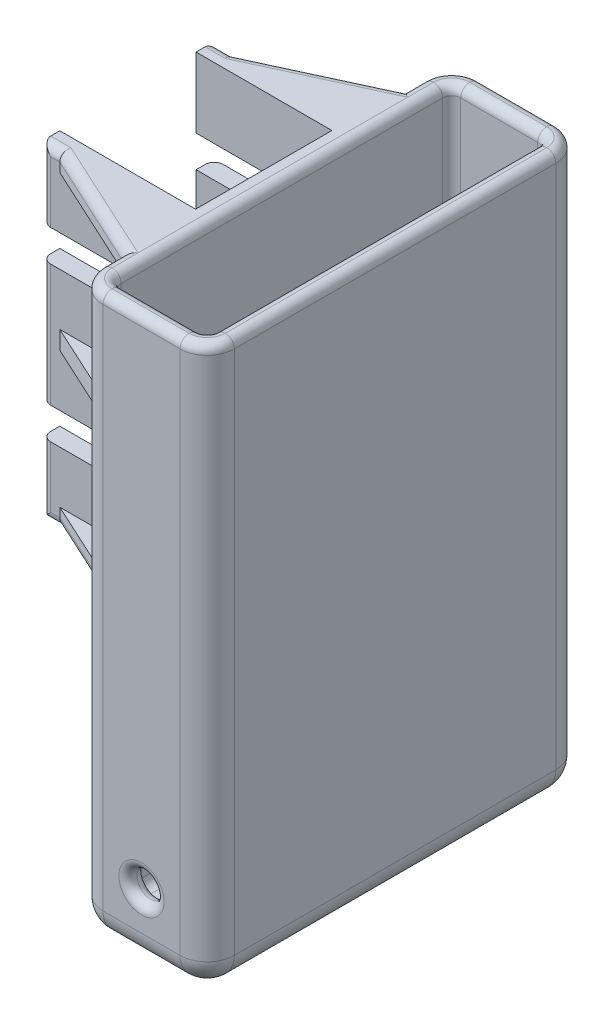
SolidWorks part; units mm, degrees
ref_plane "정면" through (0, 0, 0) normal (0, 0, 1) x (1, 0, 0)
ref_plane "윗면" through (0, 0, 0) normal (0, 1, 0) x (1, 0, 0)
ref_plane "우측면" through (0, 0, 0) normal (1, 0, 0) x (0, 0, -1)
sketch "스케치1" plane through (0, 0, 0) normal (0, 1, 0) x (1, 0, 0)
  line L1 (6, 37.5) -> (23, 37.5)
  line L2 (4, 35.5) -> (4, -35.5)
  line L3 (6, -37.5) -> (23, -37.5)
  line L4 (25, 35.5) -> (25, -35.5)
  line L5 (4, 37.5) -> (25, -37.5) construction
  line L6 (4, -37.5) -> (25, 37.5) construction
  line L7 (6, 41.5) -> (23, 41.5)
  line L8 (0, 35.5) -> (0, -35.5)
  line L9 (6, -41.5) -> (23, -41.5)
  line L10 (29, 35.5) -> (29, -35.5)
  line L11 (0, 41.5) -> (29, -41.5) construction
  line L12 (0, -41.5) -> (29, 41.5) construction
  arc A0 (23, -37.5) -> (25, -35.5) centre (23, -35.5) ccw
  arc A1 (4, -35.5) -> (6, -37.5) centre (6, -35.5) ccw
  arc A2 (23, 37.5) -> (25, 35.5) centre (23, 35.5) cw
  arc A3 (6, 37.5) -> (4, 35.5) centre (6, 35.5) ccw
  arc A4 (23, -41.5) -> (29, -35.5) centre (23, -35.5) ccw
  arc A5 (23, 41.5) -> (29, 35.5) centre (23, 35.5) cw
  arc A6 (0, -35.5) -> (6, -41.5) centre (6, -35.5) ccw
  arc A7 (6, 41.5) -> (0, 35.5) centre (6, 35.5) ccw
  point P0 (14.5, 0)
  point P5 (14.5, 0)
  point P10 (0, 0)
  dimension "D5" = 2
  dimension "D6" = 6
  dimension "D1" = 21
  dimension "D2" = 75
  dimension "D3" = 4
  dimension "D4" = 4
extrude "보스-돌출1" add sketch "스케치1" against normal blind 120
sketch "스케치2" plane through (0, -120, 0) normal (0, -1, 0) x (1, 0, 0)
  line L4 (23, 41.5) -> (6, 41.5)
  line L5 (0, 35.5) -> (0, -35.5)
  line L6 (6, -41.5) -> (23, -41.5)
  line L7 (29, -35.5) -> (29, 35.5)
  line L8 (23, 41.5) -> (6, 41.5)
  line L9 (0, 35.5) -> (0, -35.5)
  line L10 (6, -41.5) -> (23, -41.5)
  line L11 (29, -35.5) -> (29, 35.5)
  arc A4 (29, 35.5) -> (23, 41.5) centre (23, 35.5) ccw
  arc A5 (6, 41.5) -> (0, 35.5) centre (6, 35.5) ccw
  arc A6 (0, -35.5) -> (6, -41.5) centre (6, -35.5) ccw
  arc A7 (23, -41.5) -> (29, -35.5) centre (23, -35.5) ccw
  arc A8 (29, 35.5) -> (23, 41.5) centre (23, 35.5) ccw
  arc A9 (6, 41.5) -> (0, 35.5) centre (6, 35.5) ccw
  arc A10 (0, -35.5) -> (6, -41.5) centre (6, -35.5) ccw
  arc A11 (23, -41.5) -> (29, -35.5) centre (23, -35.5) ccw
  dimension "D1" = 0
extrude "보스-돌출2" add sketch "스케치2" along normal blind 4
fillet "필렛1" radius 2 8 edges at (4, -120, 0) (4.5858, -120, -36.9142) (14.5, -120, -37.5) (24.4142, -120, -36.9142) (25, -120, 0) (24.4142, -120, 36.9142) (14.5, -120, 37.5) (4.5858, -120, 36.9142)
fillet "필렛2" radius 6 8 edges at (29, -124, 0) (27.2426, -124, -39.7426) (14.5, -124, -41.5) (1.7574, -124, -39.7426) (0, -124, 0) (1.7574, -124, 39.7426) (14.5, -124, 41.5) (27.2426, -124, 39.7426)
sketch "스케치3" plane through (0, 0, 0) normal (0, 1, 0) x (1, 0, 0)
  line L0 (0, 15.05) -> (0, 19.05)
  line L1 (0, 35.5) -> (0, -35.5) construction
  line L2 (0, 19.05) -> (-30, 19.05)
  line L3 (-30, 19.05) -> (-30, 15.05)
  line L4 (-30, 15.05) -> (0, 15.05)
  line L5 (0, -15.05) -> (-30, -15.05)
  line L6 (-30, -15.05) -> (-30, -19.05)
  line L7 (-30, -19.05) -> (0, -19.05)
  line L8 (0, -19.05) -> (0, -15.05)
  line L9 (0, 15.05) -> (0, -15.05) construction
  point P10 (0, 0)
  dimension "D1" = 30.1
  dimension "D2" = 30
  dimension "D3" = 4
extrude "보스-돌출3" add sketch "스케치3" against normal blind 72
ref_plane "평면1" through (0, -36, 0) normal (0, 1, 0) x (1, 0, 0)
sketch "스케치4" plane through (0, -36, 0) normal (0, 1, 0) x (1, 0, 0)
  line L0 (0, 31.05) -> (0, 19.05)
  line L1 (0, 35.5) -> (0, 19.05) construction
  line L2 (0, 19.05) -> (-26, 19.05)
  line L3 (0, 19.05) -> (-30, 19.05) construction
  line L4 (-26, 19.05) -> (0, 31.05)
  line L5 (0, -19.05) -> (-26, -19.05)
  line L6 (-30, -19.05) -> (0, -19.05) construction
  line L7 (0, -19.05) -> (0, -35.5) construction
  line L8 (-26, -19.05) -> (0, -31.05)
  line L9 (0, -31.05) -> (0, -19.05)
  dimension "D1" = 26
  dimension "D2" = 12
  dimension "D3" = 12
  dimension "D4" = 26
extrude "보스-돌출4" add sketch "스케치4" along normal mid plane 4
sketch "스케치5" plane through (0, 0, 0) normal (0, 1, 0) x (1, 0, 0)
  line L0 (0, -31.05) -> (0, -19.05) construction
  line L1 (0, -19.05) -> (-26, -19.05) construction
  line L2 (-26, -19.05) -> (0, -31.05) construction
  line L3 (0, 31.05) -> (-26, 19.05) construction
  line L4 (-26, 19.05) -> (0, 19.05) construction
  line L5 (0, 19.05) -> (0, 31.05) construction
  line L6 (0, -31.05) -> (0, -19.05)
  line L7 (0, -19.05) -> (-26, -19.05)
  line L8 (-26, -19.05) -> (0, -31.05)
  line L9 (0, 31.05) -> (-26, 19.05)
  line L10 (-26, 19.05) -> (0, 19.05)
  line L11 (0, 19.05) -> (0, 31.05)
extrude "보스-돌출5" add sketch "스케치5" against normal blind 4
mirror "대칭 복사1" about plane through (0, -36, 0) normal (0, 1, 0) of "보스-돌출5"
sketch "스케치6" plane through (0, 0, 0) normal (0, 0, 1) x (1, 0, 0)
  line L0 (-15, -15.5) -> (-30, -15.5)
  line L1 (-30, -72) -> (-30, 0) construction
  line L2 (-30, -15.5) -> (-30, -22.5)
  line L3 (-30, -22.5) -> (-15, -22.5)
  line L4 (-15, -49.5) -> (-30, -49.5)
  line L5 (-30, -49.5) -> (-30, -56.5)
  line L6 (-30, -56.5) -> (-15, -56.5)
  line L8 (0, -34) -> (-26, -34) construction
  line L9 (0, -38) -> (-26, -38) construction
  arc A0 (-15, -22.5) -> (-15, -15.5) centre (-15, -19) ccw
  arc A1 (-15, -56.5) -> (-15, -49.5) centre (-15, -53) ccw
  dimension "D1" = 3.5
  dimension "D2" = 15
  dimension "D3" = 15
  dimension "D4" = 15
extrude "컷-돌출1" cut sketch "스케치6" against normal mid plane 44
sketch "스케치7" plane through (0, -124, 0) normal (0, -1, 0) x (1, 0, 0)
  line L0 (14.5, 26) -> (14.5, -26) construction
  line L1 (17.5, 26) -> (17.5, -26)
  line L2 (11.5, 26) -> (11.5, -26)
  line L3 (23, 35.5) -> (6, 35.5) construction
  arc A0 (17.5, 26) -> (11.5, 26) centre (14.5, 26) ccw
  arc A1 (11.5, -26) -> (17.5, -26) centre (14.5, -26) ccw
  point P2 (14.5, 0)
  point P7 (14.3729, 22.5954)
  point P8 (0, 0)
  point P10 (0, 0)
  point P13 (14.5, 35.5)
  point P14 (18.8348, 26.142)
  point P15 (0, 0)
  point P16 (14.5, 23.3963)
  point P17 (18.2628, 25.1124)
  point P18 (14.5, 25.9132)
  dimension "D1" = 3
  dimension "D2" = 52
extrude "컷-돌출2" cut sketch "스케치7" against normal blind 4
sketch "스케치8" plane through (0, 0, 0) normal (0, 0, 1) x (1, 0, 0)
  line L0 (6, -118) -> (23, -118) construction
  circle A0 centre (14.5, -109.5) radius 3
  point P2 (0, 0)
  point P5 (14.5, -118)
  dimension "D1" = 6
  dimension "D2" = 8.5
extrude "컷-돌출3" cut sketch "스케치8" against normal mid plane 84
fillet "필렛3" radius 2 43 edges at (24.4142, 0, 36.9142) (14.5, 0, 37.5) (4.5858, 0, 36.9142) (4, 0, 0) (4.5858, 0, -36.9142) (14.5, 0, -37.5) (24.4142, 0, -36.9142) (0, 0, 33.275) (1.7574, 0, 39.7426) (14.5, 0, 41.5) (27.2426, 0, 39.7426) (29, 0, 0) (27.2426, 0, -39.7426) (14.5, 0, -41.5) (1.7574, 0, -39.7426) (25, 0, 0) (0, 0, -33.275) (-13, -72, 25.05) (-28, -72, 19.05) (-13, -72, -25.05) (-28, -72, -19.05) (-13, 0, 25.05) (-28, 0, 19.05) (-28, 0, -19.05) (-13, 0, -25.05) (-30, -7.75, -19.05) (-30, -36, -19.05) (-30, -64.25, -19.05) (-30, -64.25, 19.05) (-30, -36, 19.05) (-30, -7.75, 19.05) (14.5, -120, -29) (11.5, -120, 0) (14.5, -120, 29) (14.5, -124, -29) (11.5, -124, 0) (14.5, -124, 29) (17.5, -120, 0) (17.5, -124, 0) (11.5, -109.5, -37.5) (11.5, -109.5, -41.5) (17.5, -109.5, 37.5) (17.5, -109.5, 41.5)
